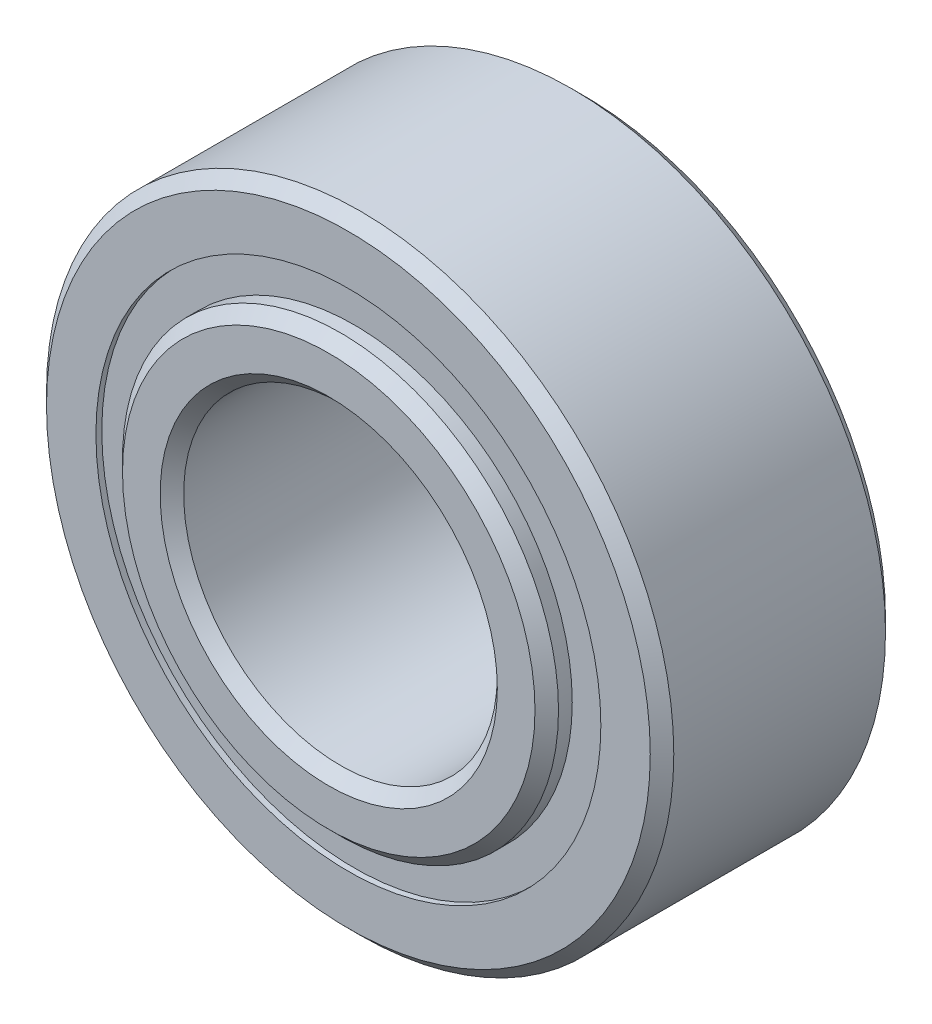
SolidWorks part; units mm, degrees
material "Cast Alloy Steel"
ref_plane "Front Plane" through (0, 0, 0) normal (0, 0, 1) x (1, 0, 0)
ref_plane "Top Plane" through (0, 0, 0) normal (0, 1, 0) x (1, 0, 0)
ref_plane "Right Plane" through (0, 0, 0) normal (1, 0, 0) x (0, 0, -1)
sketch "Sketch1" plane through (0, 0, 0) normal (1, 0, 0) x (0, 0, -1)
  line L0 (-2.3813, 0) -> (2.3813, 0) construction
  line L1 (0, 6.35) -> (0, -6.35) construction
  line L2 (2.1431, 6.35) -> (-2.1431, 6.35)
  line L3 (-2.1431, 6.35) -> (-2.3813, 6.1119)
  line L4 (-2.3813, 6.1119) -> (-2.3813, 5.1114)
  line L5 (-2.3813, 5.1114) -> (-1.0583, 5.1114)
  line L6 (2.3813, 5.1114) -> (1.0583, 5.1114)
  line L7 (2.3813, 6.1119) -> (2.3813, 5.1114)
  line L8 (2.1431, 6.35) -> (2.3813, 6.1119)
  line L9 (0, 6.35) -> (0, 4.7625) construction
  line L10 (0, 4.7625) -> (0, 3.175) construction
  arc A0 (-1.0583, 5.1114) -> (1.0583, 5.1114) centre (0, 4.7625) cw
  point P14 (0, 3.175)
  dimension "Width" = 4.7625
  dimension "OD" = 12.7
  dimension "D1" = 45
  dimension "D2" = 0.2381
  dimension "Shaft Dia" = 6.35
  dimension "D3" = 2.1167
  dimension "D4" = 0.3489
revolve "Revolve1" add sketch "Sketch1" angle 360 about L0
sketch "Sketch3" plane through (0, 0, 0) normal (1, 0, 0) x (0, 0, -1)
  line L0 (-1.0583, 4.4136) -> (-2.7788, 4.4136) construction
  line L1 (-2.3813, 6.1119) -> (-2.3813, 5.1114) construction
  line L2 (-2.1431, 6.35) -> (-2.3813, 6.1119) construction
  line L3 (-2.7788, 4.4136) -> (-2.7788, 3.4131) construction
  line L4 (-2.7788, 3.4131) -> (-2.7788, 4.1755)
  line L5 (-2.7788, 3.4131) -> (-2.5406, 3.175)
  line L6 (-2.5406, 3.175) -> (2.5406, 3.175)
  line L8 (2.5406, 3.175) -> (2.7788, 3.4131)
  line L10 (2.7788, 3.4131) -> (2.7788, 4.4136) construction
  line L11 (2.7788, 4.4136) -> (1.0583, 4.4136) construction
  line L12 (0, 6.35) -> (0, -6.35) construction
  line L13 (2.1431, 6.35) -> (2.3813, 6.1119) construction
  line L14 (-2.7788, 4.1755) -> (-2.5406, 4.4136)
  line L15 (-2.5406, 4.4136) -> (-1.0583, 4.4136)
  line L16 (1.0583, 4.4136) -> (2.5406, 4.4136)
  line L17 (2.5406, 4.4136) -> (2.7788, 4.1755)
  line L18 (2.7788, 4.1755) -> (2.7788, 3.4131)
  arc A1 (1.0583, 4.4136) -> (-1.0583, 4.4136) centre (0, 4.7625) cw
  arc A2 (1.0583, 5.1114) -> (-1.0583, 5.1114) centre (0, 4.7625) ccw construction
  dimension "D1" = 45
  dimension "Ring" = 5.5575
revolve "Revolve3" add sketch "Sketch3" angle 360 about L0
sketch "Sketch4" plane through (0, 0, 0) normal (1, 0, 0) x (0, 0, -1)
  line L0 (-1.1144, 4.7625) -> (1.1144, 4.7625)
  arc A2 (-1.1144, 4.7625) -> (1.1144, 4.7625) centre (0, 4.7625) cw
  arc A3 (1.0583, 5.1114) -> (-1.0583, 5.1114) centre (0, 4.7625) ccw construction
revolve "Revolve4" add sketch "Sketch4" angle 360 about L0
ref_axis "Axis1" through (0, 0, -2.3813) along (0, 0, 1)
pattern_circular "CirPattern1" count 10 every 36 about axis through (0, 0, -2.3813) along (0, 0, 1) of bodies 104
sketch "Sketch5" plane through (0, 0, 0) normal (1, 0, 0) x (0, 0, -1)
  line L0 (-2.3813, 5.1114) -> (-1.0583, 5.1114) construction
  line L1 (-2.2622, 5.1114) -> (-1.1144, 5.1114)
  line L2 (-2.2622, 5.1114) -> (-2.2622, 4.4136)
  line L3 (-2.2622, 4.4136) -> (-1.1144, 4.4136)
  line L4 (-1.1144, 5.1114) -> (-1.1144, 4.4136)
  line L5 (-1.0583, 4.4136) -> (-2.7788, 4.4136) construction
  line L6 (2.3813, 5.1114) -> (1.0583, 5.1114) construction
  line L7 (2.2622, 5.1114) -> (1.1144, 5.1114)
  line L8 (2.2622, 5.1114) -> (2.2622, 4.4136)
  line L9 (2.2622, 4.4136) -> (1.1144, 4.4136)
  line L10 (1.1144, 5.1114) -> (1.1144, 4.4136)
  line L11 (2.7788, 4.4136) -> (1.0583, 4.4136) construction
  line L12 (-2.1431, 6.35) -> (-2.3813, 6.1119) construction
  point P18 (-2.2622, 6.2309)
revolve "Revolve5" add sketch "Sketch5" angle 360 about L0
equation "\"D2@Sketch1\" = \"Width@Sketch1\"*.05"
equation "\"D3@Sketch1\" = \"Width@Sketch1\"/2.25"
equation "\"D4@Sketch1\" = (((\"OD@Sketch1\"-\"Width@Sketch1\")/2)/3.25)/3.5"
equation "\"D2@CirPattern1\" = 360/\"Balls@CirPattern1\""
